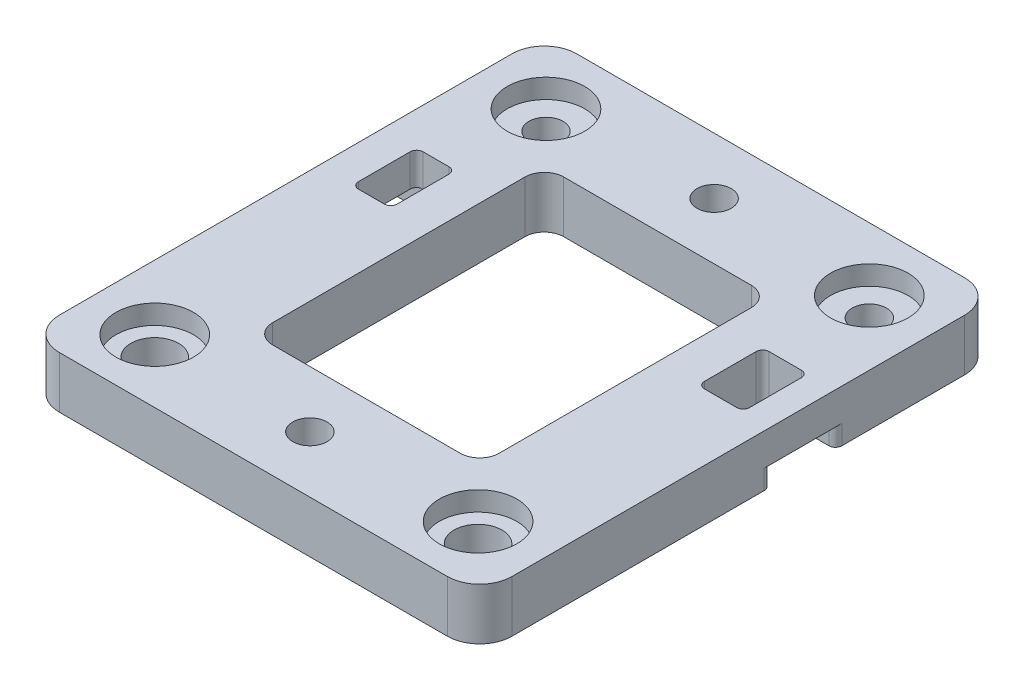
SolidWorks part; units mm, degrees
ref_plane "Alzado" through (0, 0, 0) normal (0, 0, 1) x (1, 0, 0)
ref_plane "Planta" through (0, 0, 0) normal (0, 1, 0) x (1, 0, 0)
ref_plane "Vista lateral" through (0, 0, 0) normal (1, 0, 0) x (0, 0, -1)
sketch "Croquis1" plane through (0, 0, 0) normal (0, 1, 0) x (1, 0, 0)
  line L0 (0, 22.5) -> (0, -22.5) construction
  line L1 (-14.5, -22.5) -> (14.5, -22.5)
  line L2 (-17.5, -19.5) -> (-17.5, 19.5)
  line L3 (-14.5, 22.5) -> (14.5, 22.5)
  line L4 (17.5, -19.5) -> (17.5, 19.5)
  line L5 (24.75, 15) -> (29.75, 15)
  line L8 (-35, -35) -> (-35, 35)
  line L9 (-30, 40) -> (30, 40)
  line L10 (35, -35) -> (35, 35)
  line L11 (23.75, 14) -> (23.75, 6)
  line L26 (-30, -40) -> (30, -40)
  line L30 (0, 22.5) -> (0, 31.2526) construction
  line L31 (0, 31.2526) -> (0, 40) construction
  line L32 (24.75, 5) -> (29.75, 5)
  line L39 (30.75, 6) -> (30.75, 14)
  line L40 (-28.75, 15) -> (-24.75, 15)
  line L41 (-28.75, 5) -> (-24.75, 5)
  line L42 (0, -22.5) -> (0, -31.2526) construction
  line L43 (0, -31.2526) -> (0, -40) construction
  line L44 (-24.9996, 30.2539) -> (24.9996, 30.2539) construction
  line L45 (24.9996, 30.2539) -> (24.9996, -30.2474) construction
  line L47 (-29.75, 6) -> (-29.75, 14)
  line L49 (-23.75, 6) -> (-23.75, 14)
  line L50 (24.9996, -30.2474) -> (-24.9996, -30.2474) construction
  line L51 (-24.9996, -30.2474) -> (-24.9996, 30.2539) construction
  line L52 (24.75, 15) -> (17.5, 15) construction
  line L53 (27.25, 5) -> (27.25, -40) construction
  line L54 (-24.75, 15) -> (-17.5, 15) construction
  line L55 (-26.75, 5) -> (-26.75, -40) construction
  arc A0 (-14.5, -22.5) -> (-17.5, -19.5) centre (-14.5, -19.5) cw
  arc A1 (17.5, -19.5) -> (14.5, -22.5) centre (14.5, -19.5) cw
  arc A2 (17.5, 19.5) -> (14.5, 22.5) centre (14.5, 19.5) ccw
  arc A3 (-14.5, 22.5) -> (-17.5, 19.5) centre (-14.5, 19.5) ccw
  circle A4 centre (0, 31.2526) radius 2.65
  circle A5 centre (0, -31.2526) radius 2.65
  circle A6 centre (-24.9996, -30.2474) radius 6
  circle A7 centre (-24.9996, -30.2474) radius 3.7
  circle A8 centre (-24.9996, 30.2539) radius 6
  circle A9 centre (-24.9996, 30.2539) radius 2.65
  circle A10 centre (24.9996, -30.2474) radius 6
  circle A11 centre (24.9996, -30.2474) radius 3.7
  circle A12 centre (24.9996, 30.2539) radius 2.65
  circle A13 centre (24.9996, 30.2539) radius 6
  arc A14 (23.75, 6) -> (24.75, 5) centre (24.75, 6) ccw
  arc A15 (29.75, 5) -> (30.75, 6) centre (29.75, 6) ccw
  arc A16 (29.75, 15) -> (30.75, 14) centre (29.75, 14) cw
  arc A17 (24.75, 15) -> (23.75, 14) centre (24.75, 14) ccw
  arc A18 (-28.75, 5) -> (-29.75, 6) centre (-28.75, 6) cw
  arc A19 (-24.75, 5) -> (-23.75, 6) centre (-24.75, 6) ccw
  arc A20 (-23.75, 14) -> (-24.75, 15) centre (-24.75, 14) ccw
  arc A21 (-28.75, 15) -> (-29.75, 14) centre (-28.75, 14) ccw
  arc A22 (-30, -40) -> (-35, -35) centre (-30, -35) cw
  arc A23 (30, -40) -> (35, -35) centre (30, -35) ccw
  arc A24 (35, 35) -> (30, 40) centre (30, 35) ccw
  arc A25 (-30, 40) -> (-35, 35) centre (-30, 35) ccw
  point P0 (0, 0)
  point P7 (0, 0)
  point P77 (0, 0)
  dimension "D1" = 3
  dimension "D2" = 5.3
  dimension "D3" = 7.4
  dimension "D4" = 12
  dimension "D5" = 5.3
  dimension "D6" = 12
  dimension "D7" = 1
  dimension "D8" = 5
  dimension "D9" = 8
  dimension "D17" = 5.3
  dimension "D10" = 4
  dimension "D11" = 15.2539
  dimension "D12" = 35
  dimension "D13" = 45
  dimension "D14" = 70
  dimension "D15" = 8.7526
  dimension "D16" = 8.7474
  dimension "D18" = 8.7526
  dimension "D19" = 49.9993
  dimension "D20" = 60.5013
  dimension "D21" = 7.25
  dimension "D22" = 5
  dimension "D23" = 8
  dimension "D24" = 45
  dimension "D25" = 7.25
extrude "Saliente-Extruir1" add sketch "Croquis1" along normal blind 8 contours L8 L26 L10 L9 A21 L40 A20 L49 A19 L41 A18 L47 A17 L5 A16 L39 A15 L32 A14 L11 A5 A4 A3 L3 A2 L4 A1 L1 A0 L2 A6 A8 A10 A13 region at (-33.937, 0, 0)
extrude "Saliente-Extruir2" add sketch "Croquis1<4>" along normal blind 5 contours A6 A7 | A8 A9 | A13 | A10 region at (-30.8299, 0, 30.2474) region at (-30.8299, 0, -30.2539)
sketch "Croquis1<4>" plane through (0, 0, 0) normal (0, 1, 0) x (1, 0, 0) same geometry as "Croquis1"
extrude "Cortar-Extruir1" cut sketch "Croquis1<6>" along normal blind 5 contours A12 | A11
sketch "Croquis1<6>" plane through (0, 0, 0) normal (0, 1, 0) x (1, 0, 0) same geometry as "Croquis1"
sketch "Croquis3" plane through (0, 0, 0) normal (0, -1, 0) x (1, 0, 0)
  line L0 (-35, -4) -> (-35, -16)
  line L1 (-28.75, -5) -> (-34, -5)
  line L2 (-28.75, -15) -> (-34, -15)
  line L3 (-28.75, -5) -> (-28.75, -15)
  line L4 (35, -4) -> (35, -16)
  line L5 (29.75, -15) -> (34, -15)
  line L6 (29.75, -5) -> (34, -5)
  line L7 (29.75, -5) -> (29.75, -15)
  arc A0 (-34, -5) -> (-35, -4) centre (-34, -4) cw
  arc A1 (-35, -16) -> (-34, -15) centre (-34, -16) cw
  arc A2 (35, -16) -> (34, -15) centre (34, -16) ccw
  arc A3 (34, -5) -> (35, -4) centre (34, -4) ccw
  point P14 (-35, -15)
  point P25 (35, -15)
  dimension "D1" = 1
  dimension "D2" = 1
  dimension "D3" = 12
  dimension "D4" = 5.25
  dimension "D5" = 4.25
  dimension "D6" = 12
extrude "Cortar-Extruir2" cut sketch "Croquis3" against normal blind 3
